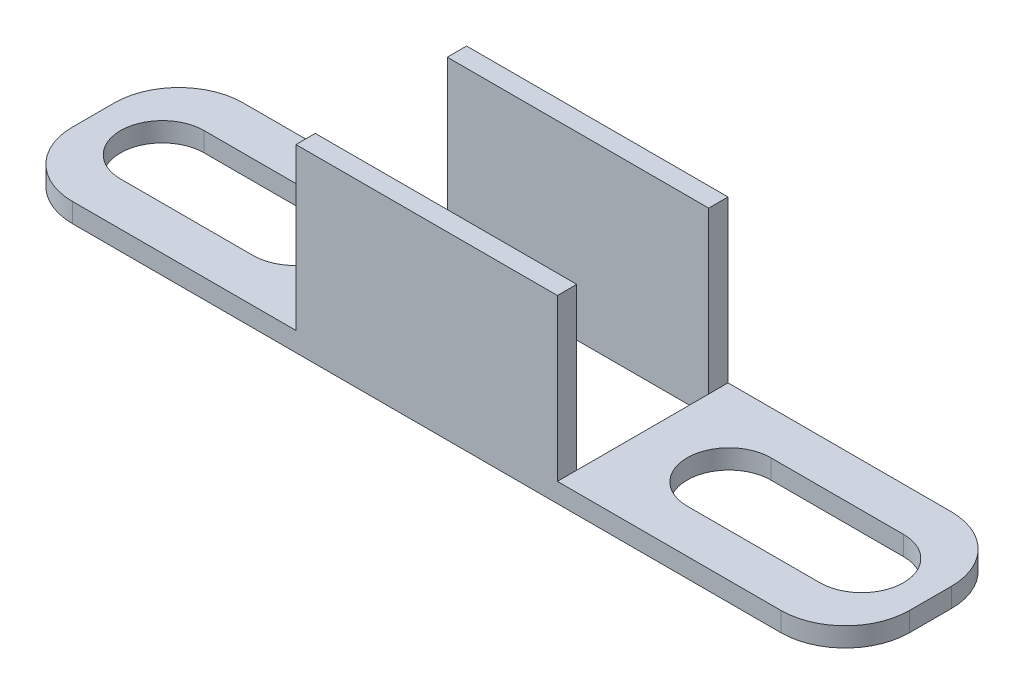
SolidWorks part; units mm, degrees
ref_plane "Front Plane" through (0, 0, 0) normal (0, 0, 1) x (1, 0, 0)
ref_plane "Top Plane" through (0, 0, 0) normal (0, 1, 0) x (1, 0, 0)
ref_plane "Right Plane" through (0, 0, 0) normal (1, 0, 0) x (0, 0, -1)
sketch "Sketch1" plane through (0, 0, 0) normal (0, 1, 0) x (1, 0, 0)
  line L0 (33.7, 0) -> (54.3, 0) construction
  line L1 (-20.3, -10.25) -> (20.3, -10.25)
  line L2 (-20.3, -10.25) -> (-20.3, 10.25)
  line L3 (-20.3, 10.25) -> (20.3, 10.25)
  line L4 (20.3, -10.25) -> (20.3, 10.25)
  line L5 (-20.3, -10.25) -> (20.3, 10.25) construction
  line L6 (-20.3, 10.25) -> (20.3, -10.25) construction
  line L7 (-65, -13.25) -> (65, -13.25)
  line L8 (-65, -13.25) -> (-65, 13.25)
  line L9 (-65, 13.25) -> (65, 13.25)
  line L10 (65, -13.25) -> (65, 13.25)
  line L11 (-65, -13.25) -> (65, 13.25) construction
  line L12 (-65, 13.25) -> (65, -13.25) construction
  line L13 (33.7, 6.5) -> (54.3, 6.5)
  line L14 (33.7, -6.5) -> (54.3, -6.5)
  line L15 (-33.7, 0) -> (-54.3, 0) construction
  line L16 (-33.7, -6.5) -> (-54.3, -6.5)
  line L17 (-33.7, 6.5) -> (-54.3, 6.5)
  arc A0 (33.7, 6.5) -> (33.7, -6.5) centre (33.7, 0) ccw
  arc A1 (54.3, -6.5) -> (54.3, 6.5) centre (54.3, 0) ccw
  arc A2 (-33.7, -6.5) -> (-33.7, 6.5) centre (-33.7, 0) ccw
  arc A3 (-54.3, 6.5) -> (-54.3, -6.5) centre (-54.3, 0) ccw
  point P0 (0, 0)
  point P6 (0, 0)
  point P13 (44, 0)
  point P18 (-44, 0)
  point P25 (0, 0)
  point P26 (0, 0)
  dimension "D6" = 20.6
  dimension "D9" = 67.4
  dimension "D10" = 33.7
  dimension "D1" = 40.6
  dimension "D2" = 20.5
  dimension "D3" = 130
  dimension "D4" = 26.5
  dimension "D5" = 13
  dimension "D7" = 20.6
  dimension "D8" = 13
extrude "Boss-Extrude1" add sketch "Sketch1" along normal blind 3
sketch "Sketch2" plane through (0, 3, 0) normal (0, 1, 0) x (1, 0, 0)
  line L0 (-65, -13.25) -> (65, -13.25) construction
  line L1 (-20.3, -10.25) -> (20.3, -10.25)
  line L2 (-20.3, -10.25) -> (-20.3, -13.25)
  line L3 (-20.3, -13.25) -> (20.3, -13.25)
  line L4 (20.3, -10.25) -> (20.3, -13.25)
  line L5 (65, 13.25) -> (-65, 13.25) construction
  line L6 (-20.3, 10.25) -> (20.3, 10.25)
  line L7 (-20.3, 10.25) -> (-20.3, 13.25)
  line L8 (-20.3, 13.25) -> (20.3, 13.25)
  line L9 (20.3, 10.25) -> (20.3, 13.25)
  dimension "D1" = 40.6
  dimension "D2" = 40.6
extrude "Boss-Extrude2" add sketch "Sketch2" along normal blind 25
fillet "Fillet1" radius 10 4 edges at (65, 1.5, -13.25) (65, 1.5, 13.25) (-65, 1.5, -13.25) (-65, 1.5, 13.25)
